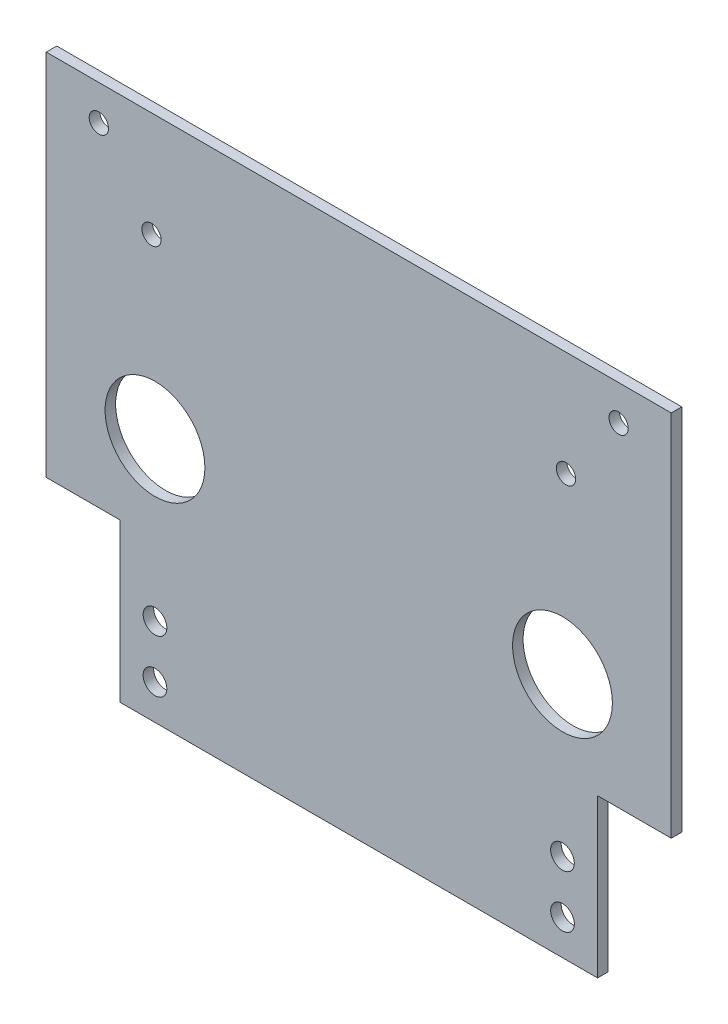
SolidWorks part; units mm, degrees
ref_plane "Front Plane" through (0, 0, 0) normal (0, 0, 1) x (1, 0, 0)
ref_plane "Top Plane" through (0, 0, 0) normal (0, 1, 0) x (1, 0, 0)
ref_plane "Right Plane" through (0, 0, 0) normal (1, 0, 0) x (0, 0, -1)
sketch "Sketch1" plane through (0, 0, 0) normal (0, 0, 1) x (1, 0, 0)
  line L1 (0, 0) -> (178.16, 0)
  line L2 (0, 0) -> (0, -150)
  line L3 (0, -150) -> (178.16, -150)
  line L4 (178.16, 0) -> (178.16, -150)
  dimension "D1" = 150
  dimension "D2" = 178.16
extrude "Boss-Extrude1" add sketch "Sketch1" along normal blind 3
sketch "Sketch2" plane through (0, 0, 3) normal (0, 0, 1) x (1, 0, 0)
  line L0 (0, 0) -> (0, -150) construction
  line L1 (178.16, -150) -> (178.16, 0) construction
  line L2 (0, -150) -> (178.16, -150) construction
  line L3 (178.16, 0) -> (0, 0) construction
  circle A0 centre (31, -80) radius 14.225
  circle A1 centre (147.16, -80) radius 14.225
  circle A3 centre (31, -140) radius 3.375
  circle A4 centre (147.16, -140) radius 3.375
  circle A8 centre (31, -125) radius 3.375
  circle A9 centre (147.16, -125) radius 3.375
  dimension "D1" = 28.45
  dimension "D2" = 28.45
  dimension "D3" = 10
  dimension "D4" = 6.75
  dimension "D7" = 6.75
  dimension "D14" = 6.75
  dimension "D17" = 6.75
  dimension "D9" = 31
  dimension "D10" = 31
  dimension "D12" = 80
  dimension "D15" = 15
  dimension "D16" = 15
extrude "Cut-Extrude1" cut sketch "Sketch2" against normal through all
sketch "Sketch4" plane through (0, 0, 3) normal (0, 0, 1) x (1, 0, 0)
  line L1 (21, -150) -> (21, -105)
  line L2 (21, -105) -> (0, -105)
  line L3 (0, 0) -> (0, -150) construction
  line L4 (0, -105) -> (0, -150)
  line L5 (0, -150) -> (21, -150)
  line L6 (0, -150) -> (178.16, -150) construction
  line L8 (178.16, -150) -> (157.16, -150)
  line L9 (178.16, -150) -> (178.16, -105)
  line L10 (178.16, -105) -> (157.16, -105)
  line L11 (157.16, -150) -> (157.16, -105)
  dimension "D1" = 45
  dimension "D2" = 21
  dimension "D3" = 21
  dimension "D4" = 45
extrude "Cut-Extrude3" cut sketch "Sketch4" against normal through all
sketch "Sketch5" plane through (0, 0, 3) normal (0, 0, 1) x (1, 0, 0)
  line L0 (178.16, 0) -> (0, 0) construction
  line L1 (178.16, -105) -> (178.16, 0) construction
  line L2 (0, 0) -> (0, -105) construction
  circle A0 centre (163.16, -10) radius 2.75
  circle A1 centre (15, -10) radius 2.75
  circle A3 centre (148.16, -30) radius 2.75
  circle A4 centre (30, -30) radius 2.75
  dimension "D3" = 5.5
  dimension "D4" = 5.5
  dimension "D5" = 5.5
  dimension "D6" = 5.5
  dimension "D1" = 10
  dimension "D2" = 30
  dimension "D7" = 15
  dimension "D8" = 15
  dimension "D9" = 30
  dimension "D10" = 30
extrude "Cut-Extrude4" cut sketch "Sketch5" against normal through all
